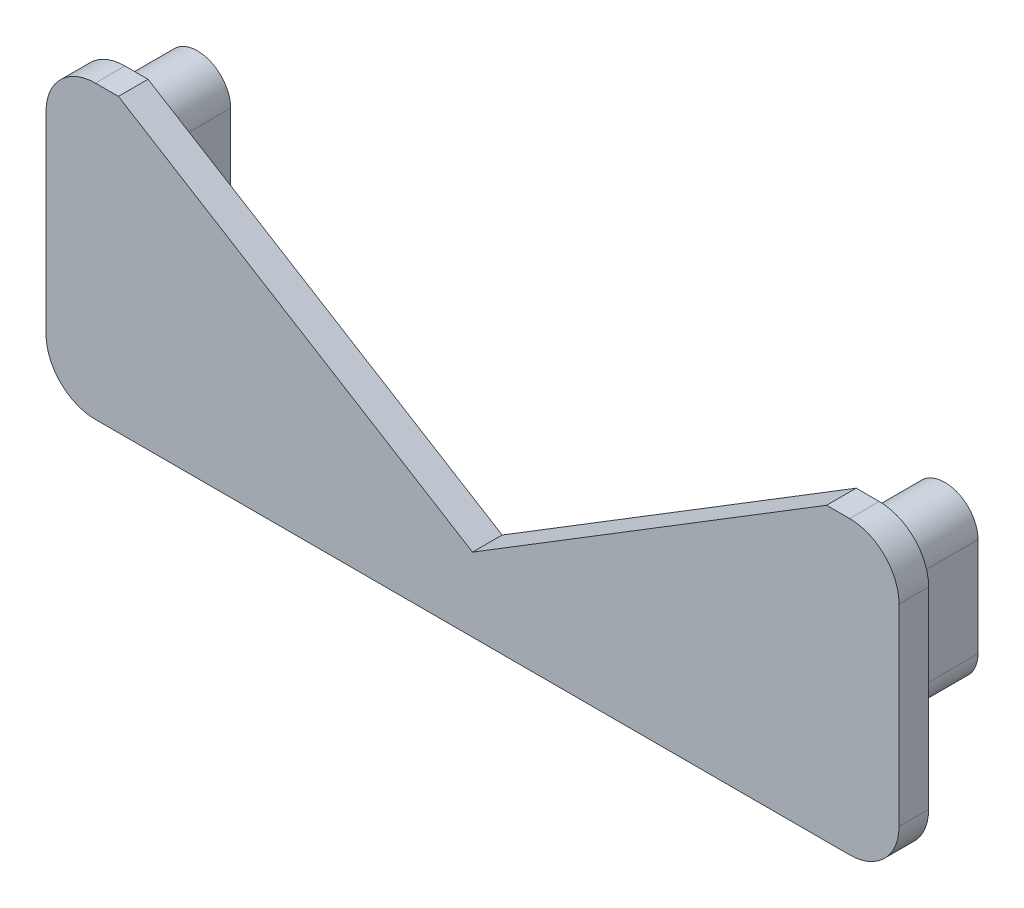
SolidWorks part; units mm, degrees
ref_plane "Front Plane" through (0, 0, 0) normal (0, 0, 1) x (1, 0, 0)
ref_plane "Top Plane" through (0, 0, 0) normal (0, 1, 0) x (1, 0, 0)
ref_plane "Right Plane" through (0, 0, 0) normal (1, 0, 0) x (0, 0, -1)
sketch "Sketch1" plane through (0, 0, 0) normal (0, 0, 1) x (1, 0, 0)
  line L0 (-37.85, 9.402) -> (-37.85, -0.598) construction
  line L1 (-38.2, -14.752) -> (38.2, -14.752)
  line L2 (-43.2, -9.752) -> (-43.2, 9.752)
  line L3 (-38.2, 14.752) -> (38.2, 14.752)
  line L4 (43.2, -9.752) -> (43.2, 9.752)
  line L5 (-43.2, -14.752) -> (43.2, 14.752) construction
  line L6 (-43.2, 14.752) -> (43.2, -14.752) construction
  line L7 (-34.5, 9.402) -> (-34.5, -0.598)
  line L8 (-41.2, 9.402) -> (-41.2, -0.598)
  line L9 (37.85, 9.402) -> (37.85, -0.598) construction
  line L10 (41.2, 9.402) -> (41.2, -0.598)
  line L11 (34.5, 9.402) -> (34.5, -0.598)
  line L12 (-37.85, 4.402) -> (37.85, 4.402) construction
  line L13 (-35.866, 14.752) -> (0, -7.2917)
  line L14 (0, -7.2917) -> (35.866, 14.752)
  arc A0 (-34.5, 9.402) -> (-41.2, 9.402) centre (-37.85, 9.402) ccw
  arc A1 (-41.2, -0.598) -> (-34.5, -0.598) centre (-37.85, -0.598) ccw
  arc A2 (41.2, 9.402) -> (34.5, 9.402) centre (37.85, 9.402) ccw
  arc A3 (34.5, -0.598) -> (41.2, -0.598) centre (37.85, -0.598) ccw
  arc A4 (-38.2, -14.752) -> (-43.2, -9.752) centre (-38.2, -9.752) cw
  arc A5 (38.2, -14.752) -> (43.2, -9.752) centre (38.2, -9.752) ccw
  arc A6 (38.2, 14.752) -> (43.2, 9.752) centre (38.2, 9.752) cw
  arc A7 (-43.2, 9.752) -> (-38.2, 14.752) centre (-38.2, 9.752) cw
  point P0 (0, 0)
  point P8 (-37.85, 4.402)
  point P13 (37.85, 4.402)
  point P22 (0, 4.402)
  point P37 (1.1815, 5.7761)
  point P39 (0, 0)
  point P40 (0, -3.3758)
  point P41 (-36.35, 15.0599)
  point P42 (0, -7.2917)
  point P43 (0, 0)
  point P44 (-35.866, 14.752)
  dimension "D5" = 5
  dimension "D1" = 6.7
  dimension "D2" = 69
  dimension "D3" = 2
  dimension "D4" = 5.35
  dimension "D6" = 10
extrude "Boss-Extrude1" add sketch "Sketch1" along normal blind 3 contours L8 A1 L7 A0 | L11 A3 L10 A2 | A7 L2 A4 L1 A5 L4 A6 L3 L14 L13 A3 L11 A2 L10 A1 L8 A0 L7 region at (-41.09, -12.6419, 0) region at (-37.85, 4.402, 0) region at (37.85, 4.402, 0)
extrude "Boss-Extrude2" add sketch "Sketch1<3>" against normal blind 7 contours L11 A3 L10 A2 | L8 A1 L7 A0 region at (-37.85, 4.402, 0) region at (37.85, 4.402, 0)
sketch "Sketch1<3>" plane through (0, 0, 0) normal (0, 0, 1) x (1, 0, 0) same geometry as "Sketch1"
equation "\"D4@Sketch1\"=\"D1@Sketch1\"/2 + \"D3@Sketch1\""
